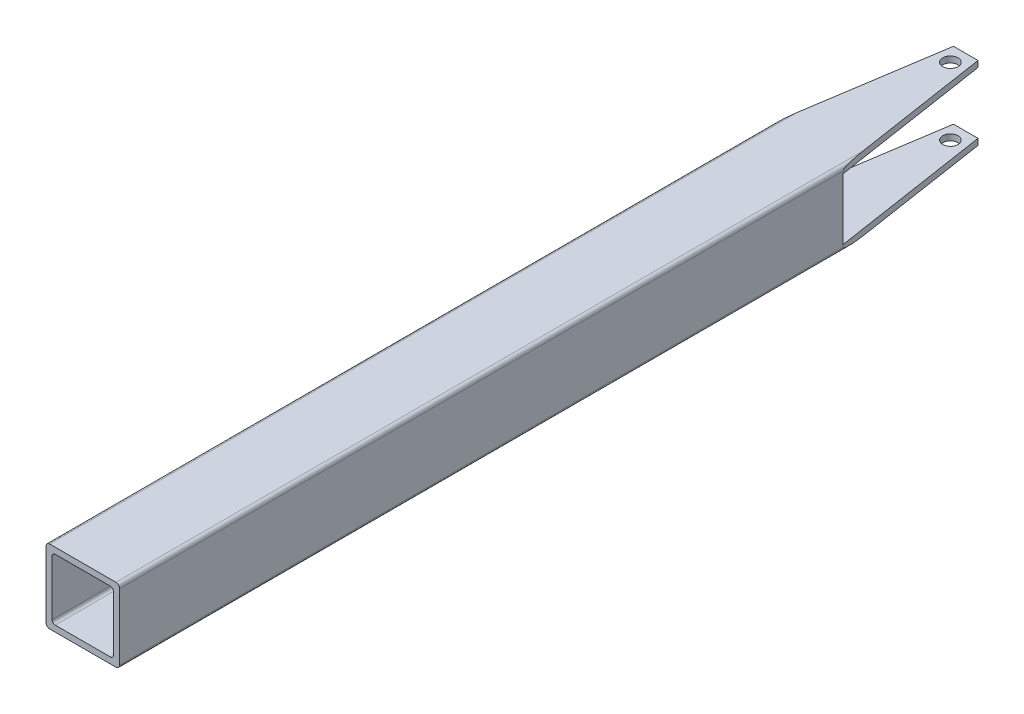
SolidWorks part; units mm, degrees
ref_plane "Front" through (0, 0, 0) normal (0, 0, 1) x (1, 0, 0)
ref_plane "Top" through (0, 0, 0) normal (0, 1, 0) x (1, 0, 0)
ref_plane "Right" through (0, 0, 0) normal (1, 0, 0) x (0, 0, -1)
sketch "Sketch1" plane through (0, 0, 0) normal (0, 0, 1) x (1, 0, 0)
  line L0 (-31.75, 0) -> (-38.1, 0) construction
  line L1 (34.29, -38.1) -> (-34.29, -38.1)
  line L2 (38.1, -34.29) -> (38.1, 34.29)
  line L3 (34.29, 38.1) -> (-34.29, 38.1)
  line L4 (-38.1, -34.29) -> (-38.1, 34.29)
  line L5 (38.1, -38.1) -> (-38.1, 38.1) construction
  line L6 (38.1, 38.1) -> (-38.1, -38.1) construction
  line L7 (28.575, 31.75) -> (-28.575, 31.75)
  line L8 (31.75, 28.575) -> (31.75, -28.575)
  line L9 (28.575, -31.75) -> (-28.575, -31.75)
  line L10 (-31.75, 28.575) -> (-31.75, -28.575)
  line L11 (31.75, 31.75) -> (-31.75, -31.75) construction
  line L12 (31.75, -31.75) -> (-31.75, 31.75) construction
  line L13 (0, -31.75) -> (0, -38.1) construction
  line L14 (31.75, -28.575) -> (31.75, -38.1) construction
  line L16 (31.75, -38.1) -> (38.1, -38.1) construction
  arc A0 (-28.575, -31.75) -> (-31.75, -28.575) centre (-28.575, -28.575) cw
  arc A1 (31.75, -28.575) -> (28.575, -31.75) centre (28.575, -28.575) cw
  arc A2 (28.575, 31.75) -> (31.75, 28.575) centre (28.575, 28.575) cw
  arc A3 (-28.575, 31.75) -> (-31.75, 28.575) centre (-28.575, 28.575) ccw
  arc A4 (34.29, -38.1) -> (38.1, -34.29) centre (34.29, -34.29) ccw
  arc A5 (38.1, 34.29) -> (34.29, 38.1) centre (34.29, 34.29) ccw
  arc A6 (-34.29, 38.1) -> (-38.1, 34.29) centre (-34.29, 34.29) ccw
  arc A7 (-34.29, -38.1) -> (-38.1, -34.29) centre (-34.29, -34.29) cw
  point P0 (0, 0)
  point P6 (0, 0)
  dimension "D2" = 3.175
  dimension "D3" = 3.81
sketch "Sketch2" plane through (0, 0, 0) normal (1, 0, 0) x (0, 0, -1)
  line L0 (-457.2, 0) -> (457.2, 0) construction
  dimension "Length" = 914.4
ref_plane "Plane1" through (38.1, 0, 0) normal (1, 0, 0) x (0, 0, -1)
sketch "Sketch5" plane through (38.1, 0, 0) normal (1, 0, 0) x (0, 0, -1)
  line L0 (-457.2, 38.1) -> (-457.2, -38.1) construction
  line L1 (457.2, 38.1) -> (457.2, -38.1) construction
sketch "Sketch4" plane through (0, 0, 0) normal (0, 0, 1) x (1, 0, 0)
  line L0 (38.1, -34.29) -> (38.1, 34.29) construction
  line L1 (34.29, 38.1) -> (-34.29, 38.1) construction
  line L2 (-38.1, -34.29) -> (-38.1, 34.29) construction
  line L3 (34.29, -38.1) -> (-34.29, -38.1) construction
  line L4 (31.75, 28.575) -> (31.75, -28.575) construction
  line L5 (28.575, -31.75) -> (-28.575, -31.75) construction
  line L6 (-31.75, 28.575) -> (-31.75, -28.575) construction
  line L7 (28.575, 31.75) -> (-28.575, 31.75) construction
  line L8 (38.1, -34.29) -> (38.1, 34.29)
  line L9 (34.29, 38.1) -> (-34.29, 38.1)
  line L10 (-38.1, -34.29) -> (-38.1, 34.29)
  line L11 (34.29, -38.1) -> (-34.29, -38.1)
  line L12 (31.75, 28.575) -> (31.75, -28.575)
  line L13 (28.575, -31.75) -> (-28.575, -31.75)
  line L14 (-31.75, 28.575) -> (-31.75, -28.575)
  line L15 (28.575, 31.75) -> (-28.575, 31.75)
  arc A0 (38.1, 34.29) -> (34.29, 38.1) centre (34.29, 34.29) ccw construction
  arc A1 (-34.29, 38.1) -> (-38.1, 34.29) centre (-34.29, 34.29) ccw construction
  arc A2 (-38.1, -34.29) -> (-34.29, -38.1) centre (-34.29, -34.29) ccw construction
  arc A3 (34.29, -38.1) -> (38.1, -34.29) centre (34.29, -34.29) ccw construction
  arc A4 (28.575, -31.75) -> (31.75, -28.575) centre (28.575, -28.575) ccw construction
  arc A5 (-31.75, -28.575) -> (-28.575, -31.75) centre (-28.575, -28.575) ccw construction
  arc A6 (-28.575, 31.75) -> (-31.75, 28.575) centre (-28.575, 28.575) ccw construction
  arc A7 (31.75, 28.575) -> (28.575, 31.75) centre (28.575, 28.575) ccw construction
  arc A8 (38.1, 34.29) -> (34.29, 38.1) centre (34.29, 34.29) ccw
  arc A9 (-34.29, 38.1) -> (-38.1, 34.29) centre (-34.29, 34.29) ccw
  arc A10 (-38.1, -34.29) -> (-34.29, -38.1) centre (-34.29, -34.29) ccw
  arc A11 (34.29, -38.1) -> (38.1, -34.29) centre (34.29, -34.29) ccw
  arc A12 (28.575, -31.75) -> (31.75, -28.575) centre (28.575, -28.575) ccw
  arc A13 (-31.75, -28.575) -> (-28.575, -31.75) centre (-28.575, -28.575) ccw
  arc A14 (-28.575, 31.75) -> (-31.75, 28.575) centre (-28.575, 28.575) ccw
  arc A15 (31.75, 28.575) -> (28.575, 31.75) centre (28.575, 28.575) ccw
extrude "Boss-Extrude1" add sketch "Sketch4" along normal up to vertex (457.2 mm away) and the other way up to vertex (457.2 mm away) up to point (0, 0, 457.2) other way up to point (0, 0, -457.2)
sketch "Sketch6" plane through (-38.1, 0, 0) normal (-1, 0, 0) x (0, 0, 1)
  line L0 (-457.2, -31.75) -> (-371.4675, -31.75) construction
  line L1 (-457.2, 31.75) -> (-292.1, 31.75)
  line L2 (-457.2, 31.75) -> (-457.2, -31.75)
  line L3 (-457.2, -31.75) -> (-292.1, -31.75)
  line L4 (-292.1, 31.75) -> (-292.1, -31.75)
  point P5 (-457.2, -31.75)
  dimension "D1" = 165.1
extrude "side cut" cut sketch "Sketch6" against normal through all
sketch "Sketch7" plane through (0, -38.1, 0) normal (0, -1, 0) x (1, 0, 0)
  line L0 (0, -457.2) -> (0, -341.7828) construction
  line L1 (-34.29, -457.2) -> (34.29, -457.2) construction
  line L2 (-38.1, -292.1) -> (-38.1, -457.2)
  line L3 (-38.1, -457.2) -> (-12.7, -457.2)
  line L4 (-12.7, -457.2) -> (-38.1, -292.1)
  line L5 (12.7, -457.2) -> (38.1, -292.1)
  line L6 (38.1, -457.2) -> (12.7, -457.2)
  line L7 (38.1, -292.1) -> (38.1, -457.2)
  dimension "D1" = 25.4
extrude "triangle cut" cut sketch "Sketch7" against normal through all
sketch "Sketch8" plane through (0, 38.1, 0) normal (0, 1, 0) x (1, 0, 0)
  line L0 (0, 457.2) -> (0, 353.4841) construction
  line L1 (12.7, 457.2) -> (-12.7, 457.2) construction
  circle A0 centre (0, 441.325) radius 7.9375
  dimension "D1" = 15.875
  dimension "D2" = 15.875
extrude "Cut-Extrude4" cut sketch "Sketch8" against normal through all
sketch "Sketch9" plane through (38.1, 0, 0) normal (1, 0, 0) x (0, 0, -1)
  line L0 (433.3875, 34.925) -> (449.2625, 34.925) construction
  line L1 (433.3875, 38.1) -> (433.3875, 31.75) construction
  line L2 (449.2625, 31.75) -> (449.2625, 38.1) construction
  line L3 (433.3875, -34.925) -> (449.2625, -34.925) construction
  line L4 (433.3875, -31.75) -> (433.3875, -38.1) construction
  line L5 (449.2625, -38.1) -> (449.2625, -31.75) construction
  line L6 (441.325, -34.925) -> (441.325, 34.925) construction
  line L7 (441.325, 0) -> (-249.555, 0)
  point P18 (-249.555, 0)
  dimension "D1" = 690.88
equation "\"D3@Sketch1\"=\"Outside Width@Sketch1\"*.05"
equation "\"D2@Sketch1\"=\"D1@Sketch1\"*.05"
equation "\"mountingPointDistance\"=27.2"
equation "\"D1@Sketch9\"=\"mountingPointDistance\""
